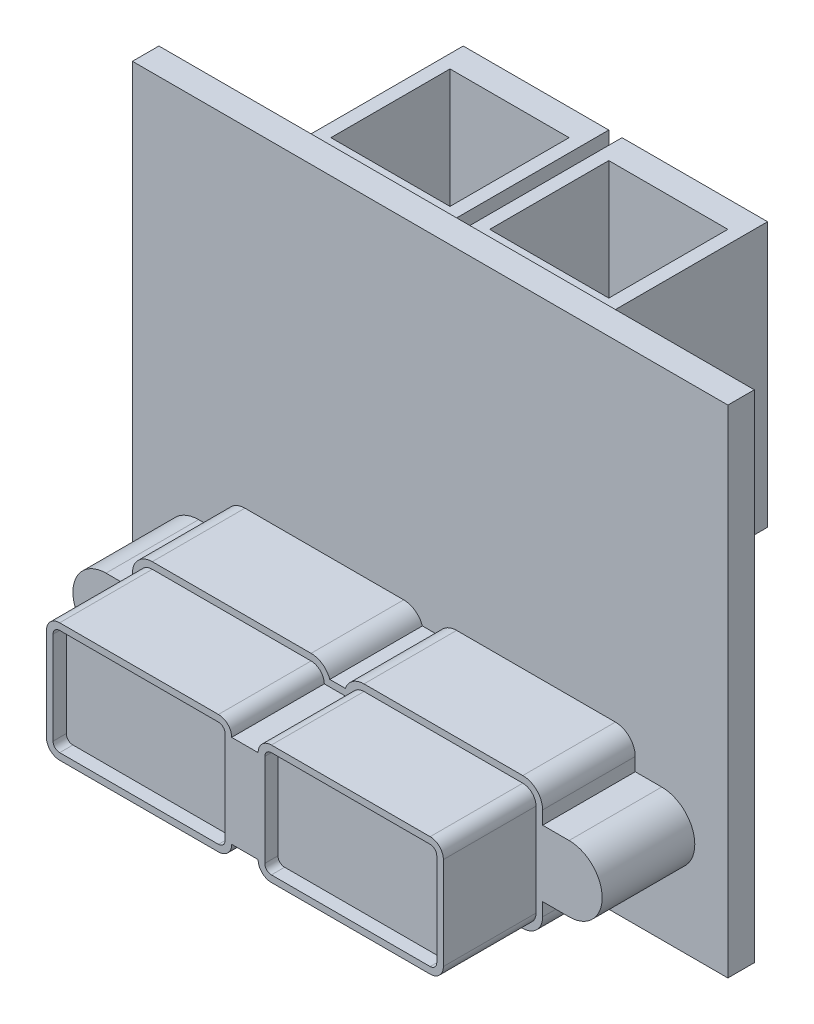
SolidWorks part; units mm, degrees
ref_plane "Front Plane" through (0, 0, 0) normal (0, 0, 1) x (1, 0, 0)
ref_plane "Top Plane" through (0, 0, 0) normal (0, 1, 0) x (1, 0, 0)
ref_plane "Right Plane" through (0, 0, 0) normal (1, 0, 0) x (0, 0, -1)
sketch "Sketch1" plane through (0, 0, 0) normal (0, 0, 1) x (1, 0, 0)
  line L1 (-22.5, 18.75) -> (22.5, 18.75)
  line L2 (-22.5, 18.75) -> (-22.5, -18.75)
  line L3 (-22.5, -18.75) -> (22.5, -18.75)
  line L4 (22.5, 18.75) -> (22.5, -18.75)
  line L5 (-22.5, 18.75) -> (22.5, -18.75) construction
  line L6 (-22.5, -18.75) -> (22.5, 18.75) construction
  point P0 (0, 0)
  dimension "D1" = 37.5
  dimension "D2" = 45
extrude "Boss-Extrude1" add sketch "Sketch1" along normal blind 2
sketch "Sketch2" plane through (0, 0, 2) normal (0, 0, 1) x (1, 0, 0)
  line L0 (0, 18.75) -> (0, -18.75) construction
  line L1 (22.5, 18.75) -> (-22.5, 18.75) construction
  line L2 (-22.5, -18.75) -> (22.5, -18.75) construction
  line L4 (-20, -4.75) -> (20, -4.75)
  line L5 (-20, -4.75) -> (-20, -17.75)
  line L6 (-20, -17.75) -> (20, -17.75)
  line L7 (20, -4.75) -> (20, -17.75)
  line L8 (-20, -4.75) -> (20, -17.75) construction
  line L9 (-20, -17.75) -> (20, -4.75) construction
  point P6 (0, -11.25)
  dimension "D1" = 13
  dimension "D2" = 40
  dimension "D3" = 1
extrude "Boss-Extrude2" add sketch "Sketch2" along normal blind 7
sketch "Sketch3" plane through (0, 0, 9) normal (0, 0, 1) x (1, 0, 0)
  line L0 (0, -4.75) -> (0, -17.75) construction
  line L1 (20, -4.75) -> (-20, -4.75) construction
  line L2 (-20, -17.75) -> (20, -17.75) construction
  line L3 (-1, -7.75) -> (-1, -6.75)
  line L4 (1, -6.75) -> (15, -6.75)
  line L5 (1, -7.75) -> (1, -6.75)
  line L6 (1, -15.75) -> (15, -15.75)
  line L7 (15, -6.75) -> (15, -15.75)
  line L8 (-1, -6.75) -> (-15, -6.75)
  line L9 (1, -14.75) -> (1, -15.75)
  line L10 (-1, -15.75) -> (-15, -15.75)
  line L11 (-15, -6.75) -> (-15, -15.75)
  line L12 (1, -7.75) -> (-1, -7.75)
  line L13 (-1, -14.75) -> (-1, -15.75)
  line L14 (1, -14.75) -> (-1, -14.75)
  line L15 (-20, -17.75) -> (20, -17.75) construction
  point P20 (0, -7.75)
  point P24 (0, -14.75)
  dimension "D1" = 2
  dimension "D2" = 2
  dimension "D3" = 30
  dimension "D5" = 2
  dimension "D6" = 1
  dimension "D7" = 1
extrude "Boss-Extrude3" add sketch "Sketch3" along normal blind 7
fillet "Fillet1" radius 1 8 edges at (-15, -15.75, 12.5) (-1, -15.75, 12.5) (1, -15.75, 12.5) (-15, -6.75, 12.5) (15, -15.75, 12.5) (15, -6.75, 12.5) (1, -6.75, 12.5) (-1, -6.75, 12.5)
sketch "Sketch4" plane through (0, 0, 16) normal (0, 0, 1) x (1, 0, 0)
  line L0 (-1.5, -14.75) -> (-1.5, -7.75)
  line L1 (1.5, -7.75) -> (1.5, -14.75)
  line L48 (-14.5, -7.75) -> (-14.5, -14.75)
  line L49 (-14, -15.25) -> (-2, -15.25)
  line L51 (-2, -14.25) -> (2, -14.25)
  line L53 (2, -15.25) -> (14, -15.25)
  line L54 (14.5, -14.75) -> (14.5, -7.75)
  line L55 (14, -7.25) -> (2, -7.25)
  line L57 (2, -8.25) -> (-2, -8.25)
  line L59 (-2, -7.25) -> (-14, -7.25)
  line L60 (-14.5, -7.75) -> (-14.5, -14.75)
  line L61 (-14, -15.25) -> (-2, -15.25)
  line L65 (2, -15.25) -> (14, -15.25)
  line L66 (14.5, -14.75) -> (14.5, -7.75)
  line L67 (14, -7.25) -> (2, -7.25)
  line L71 (-2, -7.25) -> (-14, -7.25)
  arc A32 (-14.5, -14.75) -> (-14, -15.25) centre (-14, -14.75) ccw
  arc A33 (-2, -15.25) -> (-2, -14.25) centre (-2, -14.75) ccw
  arc A34 (2, -14.25) -> (2, -15.25) centre (2, -14.75) ccw
  arc A35 (14, -15.25) -> (14.5, -14.75) centre (14, -14.75) ccw
  arc A36 (14.5, -7.75) -> (14, -7.25) centre (14, -7.75) ccw
  arc A37 (2, -7.25) -> (2, -8.25) centre (2, -7.75) ccw
  arc A38 (-2, -8.25) -> (-2, -7.25) centre (-2, -7.75) ccw
  arc A39 (-14, -7.25) -> (-14.5, -7.75) centre (-14, -7.75) ccw
  arc A40 (-14.5, -14.75) -> (-14, -15.25) centre (-14, -14.75) ccw
  arc A41 (-2, -15.25) -> (-1.5, -14.75) centre (-2, -14.75) ccw
  arc A42 (1.5, -14.75) -> (2, -15.25) centre (2, -14.75) ccw
  arc A43 (14, -15.25) -> (14.5, -14.75) centre (14, -14.75) ccw
  arc A44 (14.5, -7.75) -> (14, -7.25) centre (14, -7.75) ccw
  arc A45 (2, -7.25) -> (1.5, -7.75) centre (2, -7.75) ccw
  arc A46 (-1.5, -7.75) -> (-2, -7.25) centre (-2, -7.75) ccw
  arc A47 (-14, -7.25) -> (-14.5, -7.75) centre (-14, -7.75) ccw
  dimension "D1" = 0.5
extrude "Cut-Extrude1" cut sketch "Sketch4" against normal blind 1
sketch "Sketch5" plane through (0, 0, 9) normal (0, 0, 1) x (1, 0, 0)
  line L11 (-20, -4.75) -> (-20, -17.75) construction
  line L12 (20, -17.75) -> (20, -4.75) construction
  line L15 (-15.5, -7.75) -> (-15.5, -14.75)
  line L26 (-15.5, -7.75) -> (-15.5, -14.75) construction
  line L27 (-17.5, -8.75) -> (-15.5, -8.75)
  line L28 (15.5, -14.75) -> (15.5, -7.75)
  line L29 (15.5, -14.75) -> (15.5, -7.75) construction
  line L30 (-15.5, -8.75) -> (-15.5, -7.75)
  line L31 (-17.5, -13.75) -> (-15.5, -13.75)
  line L32 (-15.5, -13.75) -> (-15.5, -14.75)
  line L33 (17.5, -13.75) -> (15.5, -13.75)
  line L34 (15.5, -13.75) -> (15.5, -14.75)
  line L35 (17.5, -8.75) -> (15.5, -8.75)
  line L36 (15.5, -8.75) -> (15.5, -7.75)
  line L41 (14, -6.25) -> (2, -6.25)
  line L42 (-2, -6.25) -> (-14, -6.25)
  line L43 (0.5858, -7.25) -> (-0.5858, -7.25)
  line L44 (14, -6.25) -> (2, -6.25)
  line L45 (-2, -6.25) -> (-14, -6.25)
  line L46 (0.5858, -7.25) -> (-0.5858, -7.25)
  line L51 (20.5, -18.25) -> (20.5, -4.25)
  line L52 (-20.5, -18.25) -> (20.5, -18.25)
  line L53 (-20.5, -4.25) -> (-20.5, -18.25)
  line L54 (20.5, -4.25) -> (-20.5, -4.25)
  line L55 (20.5, -18.25) -> (20.5, -4.25)
  line L56 (-20.5, -18.25) -> (20.5, -18.25)
  line L57 (-20.5, -4.25) -> (-20.5, -18.25)
  line L58 (20.5, -4.25) -> (-20.5, -4.25)
  line L65 (2, -16.25) -> (14, -16.25)
  line L66 (-14, -16.25) -> (-2, -16.25)
  line L67 (-0.5858, -15.25) -> (0.5858, -15.25)
  line L68 (2, -16.25) -> (14, -16.25)
  line L69 (-14, -16.25) -> (-2, -16.25)
  line L70 (-0.5858, -15.25) -> (0.5858, -15.25)
  circle A4 centre (-17.5, -11.25) radius 2.5 construction
  circle A5 centre (17.5, -11.25) radius 2.5 construction
  arc A14 (-15.5, -14.75) -> (-14, -16.25) centre (-14, -14.75) ccw
  arc A15 (-14, -6.25) -> (-15.5, -7.75) centre (-14, -7.75) ccw
  arc A16 (-15.5, -14.75) -> (-14, -16.25) centre (-14, -14.75) ccw
  arc A17 (-14, -6.25) -> (-15.5, -7.75) centre (-14, -7.75) ccw
  arc A18 (-17.5, -13.75) -> (-17.5, -8.75) centre (-17.5, -11.25) cw
  arc A19 (17.5, -8.75) -> (17.5, -13.75) centre (17.5, -11.25) cw
  arc A20 (14, -16.25) -> (15.5, -14.75) centre (14, -14.75) ccw
  arc A21 (15.5, -7.75) -> (14, -6.25) centre (14, -7.75) ccw
  arc A22 (14, -16.25) -> (15.5, -14.75) centre (14, -14.75) ccw
  arc A23 (15.5, -7.75) -> (14, -6.25) centre (14, -7.75) ccw
  arc A32 (2, -6.25) -> (0.5858, -7.25) centre (2, -7.75) ccw
  arc A33 (-0.5858, -7.25) -> (-2, -6.25) centre (-2, -7.75) ccw
  arc A34 (2, -6.25) -> (0.5858, -7.25) centre (2, -7.75) ccw
  arc A35 (-0.5858, -7.25) -> (-2, -6.25) centre (-2, -7.75) ccw
  arc A41 (0.5858, -15.25) -> (2, -16.25) centre (2, -14.75) ccw
  arc A42 (-2, -16.25) -> (-0.5858, -15.25) centre (-2, -14.75) ccw
  arc A43 (0.5858, -15.25) -> (2, -16.25) centre (2, -14.75) ccw
  arc A44 (-2, -16.25) -> (-0.5858, -15.25) centre (-2, -14.75) ccw
  point P13 (-20, -11.25)
  dimension "D3" = 5
  dimension "D4" = 0.5
  dimension "D5" = 0.5
  dimension "D6" = 0.5
  dimension "D7" = 0.5
  dimension "D8" = 0.5
extrude "Cut-Extrude2" cut sketch "Sketch5" against normal up to surface (7 mm away) up to face at (0, 0, 2)
sketch "Sketch6" plane through (0, 0, 0) normal (0, 0, -1) x (-1, 0, 0)
  line L0 (0, 18.75) -> (0, -18.75) construction
  line L1 (-22.5, 18.75) -> (22.5, 18.75) construction
  line L2 (22.5, -18.75) -> (-22.5, -18.75) construction
  line L3 (-0.5, 18.25) -> (-0.5, -1.75)
  line L4 (-11.5, 18.25) -> (11.5, 18.25) construction
  line L5 (-11.5, 18.25) -> (-11.5, -1.75)
  line L6 (-11.5, -1.75) -> (11.5, -1.75) construction
  line L7 (11.5, 18.25) -> (11.5, -1.75)
  line L8 (-11.5, 18.25) -> (11.5, -1.75) construction
  line L9 (-11.5, -1.75) -> (11.5, 18.25) construction
  line L10 (-0.5, -1.75) -> (-11.5, -1.75)
  line L11 (-11.5, 18.25) -> (-0.5, 18.25)
  line L12 (11.5, 18.25) -> (0.5, 18.25)
  line L13 (0.5, 18.25) -> (0.5, -1.75)
  line L14 (0.5, -1.75) -> (11.5, -1.75)
  point P6 (0, 8.25)
  dimension "D1" = 20
  dimension "D2" = 23
  dimension "D3" = 11
  dimension "D4" = 0.5
extrude "Boss-Extrude5" add sketch "Sketch6" along normal blind 12
sketch "Sketch7" plane through (0, 18.25, 0) normal (0, 1, 0) x (1, 0, 0)
  line L0 (-11.5, 12) -> (-0.5, 12) construction
  line L1 (-10.5, 10) -> (-1.5, 10)
  line L2 (-10.5, 10) -> (-10.5, 1)
  line L3 (-10.5, 1) -> (-1.5, 1)
  line L4 (-1.5, 10) -> (-1.5, 1)
  line L5 (1.5, 10) -> (10.5, 10)
  line L6 (1.5, 10) -> (1.5, 1)
  line L7 (1.5, 1) -> (10.5, 1)
  line L8 (10.5, 10) -> (10.5, 1)
  line L9 (-11.5, 12) -> (-11.5, 0) construction
  line L10 (-0.5, 12) -> (-0.5, 0) construction
  line L11 (0.5, 12) -> (0.5, 0) construction
  line L12 (0.5, 0) -> (11.5, 0) construction
  dimension "D1" = 2
  dimension "D2" = 1
  dimension "D3" = 1
  dimension "D4" = 1
  dimension "D5" = 1
extrude "Cut-Extrude3" cut sketch "Sketch7" against normal blind 12
